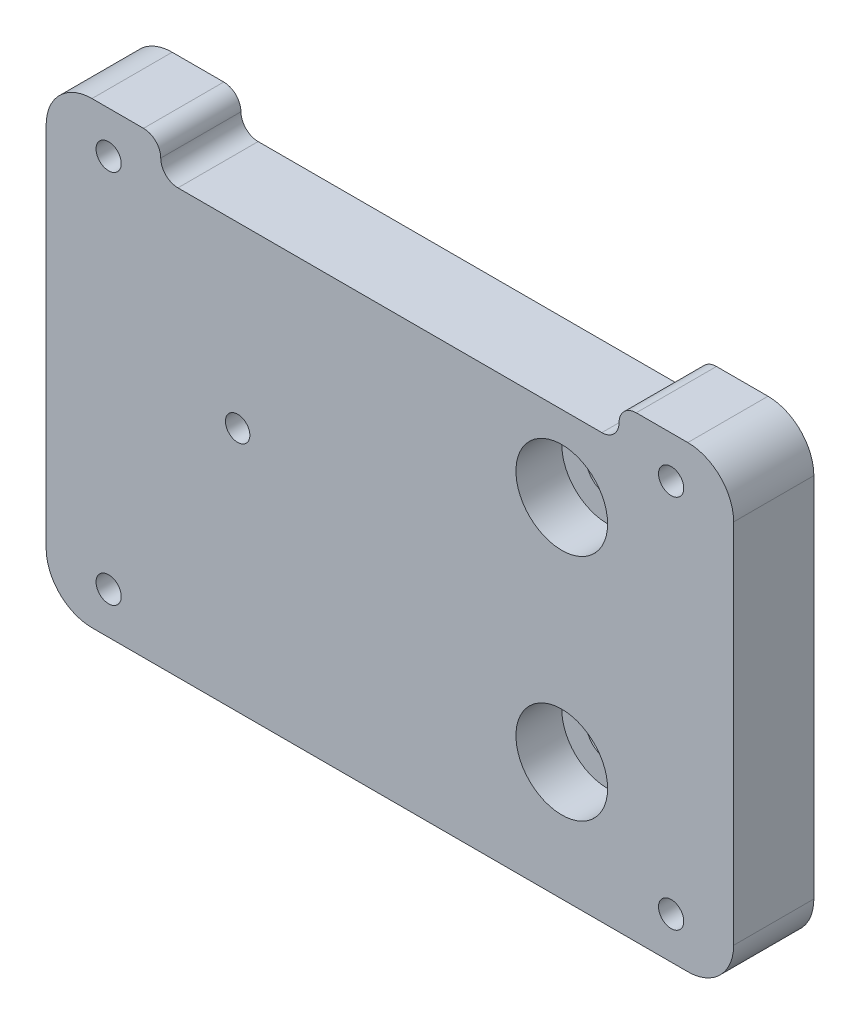
SolidWorks part; units mm, degrees
material "PET"
ref_plane "Front Plane" through (0, 0, 0) normal (0, 0, 1) x (1, 0, 0)
ref_plane "Top Plane" through (0, 0, 0) normal (0, 1, 0) x (1, 0, 0)
ref_plane "Right Plane" through (0, 0, 0) normal (1, 0, 0) x (0, 0, -1)
sketch "Sketch1" plane through (0, 0, 0) normal (0, 0, 1) x (1, 0, 0)
  line L0 (-31.1728, -20.7818) -> (0, 0) construction
  line L1 (-38.1, -25.4) -> (38.1, -25.4)
  line L2 (-38.1, -25.4) -> (-38.1, 25.4)
  line L3 (-38.1, 25.4) -> (38.1, 25.4)
  line L4 (38.1, -25.4) -> (38.1, 25.4)
  line L5 (-38.1, -25.4) -> (38.1, 25.4) construction
  line L6 (-38.1, 25.4) -> (38.1, -25.4) construction
  line L7 (0, 0) -> (31.1728, 20.7818) construction
  circle A0 centre (-31.1728, -20.7818) radius 1.397
  circle A1 centre (31.1728, 20.7818) radius 1.397
  circle A2 centre (-31.1728, 20.7818) radius 1.397
  circle A3 centre (31.1728, -20.7818) radius 1.397
  point P0 (0, 0)
  point P15 (0, 0)
  point P16 (0, 0)
  dimension "D3" = 2.794
  dimension "D4" = 2.794
  dimension "D1" = 50.8
  dimension "D2" = 76.2
  dimension "D5" = 74.93
  dimension "D6" = 74.93
extrude "Boss-Extrude1" add sketch "Sketch1" along normal blind 8.89
fillet "Fillet1" radius 5.08 4 edges at (-38.1, 25.4, 4.445) (38.1, -25.4, 4.445) (38.1, 25.4, 4.445) (-38.1, -25.4, 4.445)
sketch "Sketch2" plane through (0, 0, 8.89) normal (0, 0, 1) x (1, 0, 0)
  line L0 (0, 0) -> (0, 25.4) construction
  line L1 (33.02, 25.4) -> (-33.02, 25.4) construction
  line L2 (19.05, -12.2531) -> (19.05, 13.1469) construction
  circle A0 centre (19.05, 13.1469) radius 2.3701
  circle A1 centre (19.05, -12.2531) radius 2.3701
  dimension "D1" = 19.05
  dimension "D2" = 25.4
extrude "Cut-Extrude1" cut sketch "Sketch2" against normal through all
sketch "Sketch3" plane through (0, 0, 8.89) normal (0, 0, 1) x (1, 0, 0)
  circle A0 centre (19.05, 13.1469) radius 5.08
  circle A1 centre (19.05, -12.2531) radius 5.08
  dimension "D1" = 10.16
  dimension "D2" = 10.16
extrude "Cut-Extrude2" cut sketch "Sketch3" against normal blind 5.08
sketch "Sketch4" plane through (0, 0, 8.89) normal (0, 0, 1) x (1, 0, 0)
  line L0 (-25.4, 25.4) -> (-25.4, 21.59)
  line L1 (33.02, 25.4) -> (-33.02, 25.4) construction
  line L2 (-25.4, 21.59) -> (25.4, 21.59)
  line L3 (25.4, 21.59) -> (25.4, 25.4)
  line L4 (0, 21.59) -> (0, 25.4) construction
  line L5 (25.4, 25.4) -> (-25.4, 25.4)
  dimension "D1" = 3.81
  dimension "D2" = 50.8
extrude "Cut-Extrude3" cut sketch "Sketch4" against normal through all
fillet "Fillet2" radius 1.905 4 edges at (25.4, 25.4, 4.445) (25.4, 21.59, 4.445) (-25.4, 25.4, 4.445) (-25.4, 21.59, 4.445)
hole_wizard "#6-32 Tapped Hole1" positions "Sketch5" profile "Sketch6" tap size "#6-32" standard "ANSI Inch" end condition through all
sketch "Sketch5" plane through (0, 0, 8.89) normal (0, 0, 1) x (1, 0, 0)
  point P0 (-16.8756, 1.8222)
sketch "Sketch6" plane through (-16.8756, 1.8222, 8.89) normal (1, 0, 0) x (0, -1, 0)
  line L0 (0, 0) -> (0, 8.89)
  line L1 (0, 8.89) -> (1.3525, 8.89)
  line L2 (1.3525, 8.89) -> (1.3525, 0)
  line L5 (1.3525, 0) -> (0, 0)
  line L11 (0, -6.35) -> (0, 107.95) construction
  dimension "Thru Tap Drill Dia." = 2.7051
  dimension "Thru Tap Drill Depth" = 8.89
cosmetic thread "Hole Thread1" parameters "D2"=3.5052
